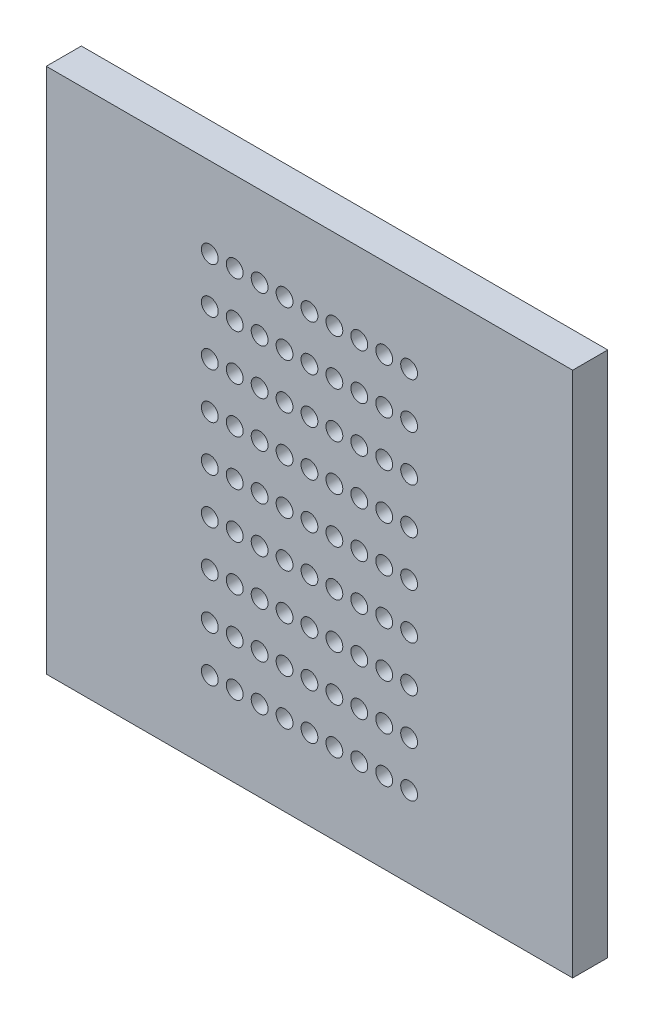
SolidWorks part; units mm, degrees
ref_plane "Plan de face" through (0, 0, 0) normal (0, 0, 1) x (1, 0, 0)
ref_plane "Plan de dessus" through (0, 0, 0) normal (0, 1, 0) x (1, 0, 0)
ref_plane "Plan de droite" through (0, 0, 0) normal (1, 0, 0) x (0, 0, -1)
sketch "Esquisse2" plane through (0, 0, 0) normal (0, 0, 1) x (1, 0, 0)
  line L1 (-15, -15) -> (15, -15)
  line L2 (-15, -15) -> (-15, 15)
  line L3 (-15, 15) -> (15, 15)
  line L4 (15, -15) -> (15, 15)
  line L5 (-15, -15) -> (15, 15) construction
  line L6 (-15, 15) -> (15, -15) construction
  point P0 (0, 0)
extrude "Boss.-Extru.1" add sketch "Esquisse2" along normal blind 2
sketch "Esquisse3" plane through (0, 0, 2) normal (0, 0, 1) x (1, 0, 0)
  circle A0 centre (-5.68, -10.4) radius 0.48
  circle A1 centre (-5.68, -7.8) radius 0.48
  circle A2 centre (-5.68, -5.2) radius 0.48
  circle A3 centre (-5.68, -2.6) radius 0.48
  circle A4 centre (-5.68, 0) radius 0.48
  circle A5 centre (-5.68, 2.6) radius 0.48
  circle A6 centre (-5.68, 5.2) radius 0.48
  circle A7 centre (-5.68, 7.8) radius 0.48
  circle A8 centre (-5.68, 10.4) radius 0.48
  circle A9 centre (-4.26, -10.4) radius 0.48
  circle A10 centre (-4.26, -7.8) radius 0.48
  circle A11 centre (-4.26, -5.2) radius 0.48
  circle A12 centre (-4.26, -2.6) radius 0.48
  circle A13 centre (-4.26, 0) radius 0.48
  circle A14 centre (-4.26, 2.6) radius 0.48
  circle A15 centre (-4.26, 5.2) radius 0.48
  circle A16 centre (-4.26, 7.8) radius 0.48
  circle A17 centre (-4.26, 10.4) radius 0.48
  circle A18 centre (-2.84, -10.4) radius 0.48
  circle A19 centre (-2.84, -7.8) radius 0.48
  circle A20 centre (-2.84, -5.2) radius 0.48
  circle A21 centre (-2.84, -2.6) radius 0.48
  circle A22 centre (-2.84, 0) radius 0.48
  circle A23 centre (-2.84, 2.6) radius 0.48
  circle A24 centre (-2.84, 5.2) radius 0.48
  circle A25 centre (-2.84, 7.8) radius 0.48
  circle A26 centre (-2.84, 10.4) radius 0.48
  circle A27 centre (-1.42, -10.4) radius 0.48
  circle A28 centre (-1.42, -7.8) radius 0.48
  circle A29 centre (-1.42, -5.2) radius 0.48
  circle A30 centre (-1.42, -2.6) radius 0.48
  circle A31 centre (-1.42, 0) radius 0.48
  circle A32 centre (-1.42, 2.6) radius 0.48
  circle A33 centre (-1.42, 5.2) radius 0.48
  circle A34 centre (-1.42, 7.8) radius 0.48
  circle A35 centre (-1.42, 10.4) radius 0.48
  circle A36 centre (0, -10.4) radius 0.48
  circle A37 centre (0, -7.8) radius 0.48
  circle A38 centre (0, -5.2) radius 0.48
  circle A39 centre (0, -2.6) radius 0.48
  circle A40 centre (0, 0) radius 0.48
  circle A41 centre (0, 2.6) radius 0.48
  circle A42 centre (0, 5.2) radius 0.48
  circle A43 centre (0, 7.8) radius 0.48
  circle A44 centre (0, 10.4) radius 0.48
  circle A45 centre (1.42, -10.4) radius 0.48
  circle A46 centre (1.42, -7.8) radius 0.48
  circle A47 centre (1.42, -5.2) radius 0.48
  circle A48 centre (1.42, -2.6) radius 0.48
  circle A49 centre (1.42, 0) radius 0.48
  circle A50 centre (1.42, 2.6) radius 0.48
  circle A51 centre (1.42, 5.2) radius 0.48
  circle A52 centre (1.42, 7.8) radius 0.48
  circle A53 centre (1.42, 10.4) radius 0.48
  circle A54 centre (2.84, -10.4) radius 0.48
  circle A55 centre (2.84, -7.8) radius 0.48
  circle A56 centre (2.84, -5.2) radius 0.48
  circle A57 centre (2.84, -2.6) radius 0.48
  circle A58 centre (2.84, 0) radius 0.48
  circle A59 centre (2.84, 2.6) radius 0.48
  circle A60 centre (2.84, 5.2) radius 0.48
  circle A61 centre (2.84, 7.8) radius 0.48
  circle A62 centre (2.84, 10.4) radius 0.48
  circle A63 centre (4.26, -10.4) radius 0.48
  circle A64 centre (4.26, -7.8) radius 0.48
  circle A65 centre (4.26, -5.2) radius 0.48
  circle A66 centre (4.26, -2.6) radius 0.48
  circle A67 centre (4.26, 0) radius 0.48
  circle A68 centre (4.26, 2.6) radius 0.48
  circle A69 centre (4.26, 5.2) radius 0.48
  circle A70 centre (4.26, 7.8) radius 0.48
  circle A71 centre (4.26, 10.4) radius 0.48
  circle A72 centre (5.68, -10.4) radius 0.48
  circle A73 centre (5.68, -7.8) radius 0.48
  circle A74 centre (5.68, -5.2) radius 0.48
  circle A75 centre (5.68, -2.6) radius 0.48
  circle A76 centre (5.68, 0) radius 0.48
  circle A77 centre (5.68, 2.6) radius 0.48
  circle A78 centre (5.68, 5.2) radius 0.48
  circle A79 centre (5.68, 7.8) radius 0.48
  circle A80 centre (5.68, 10.4) radius 0.48
extrude "Enlèv. mat.-Extru.1" cut sketch "Esquisse3" against normal blind 10
